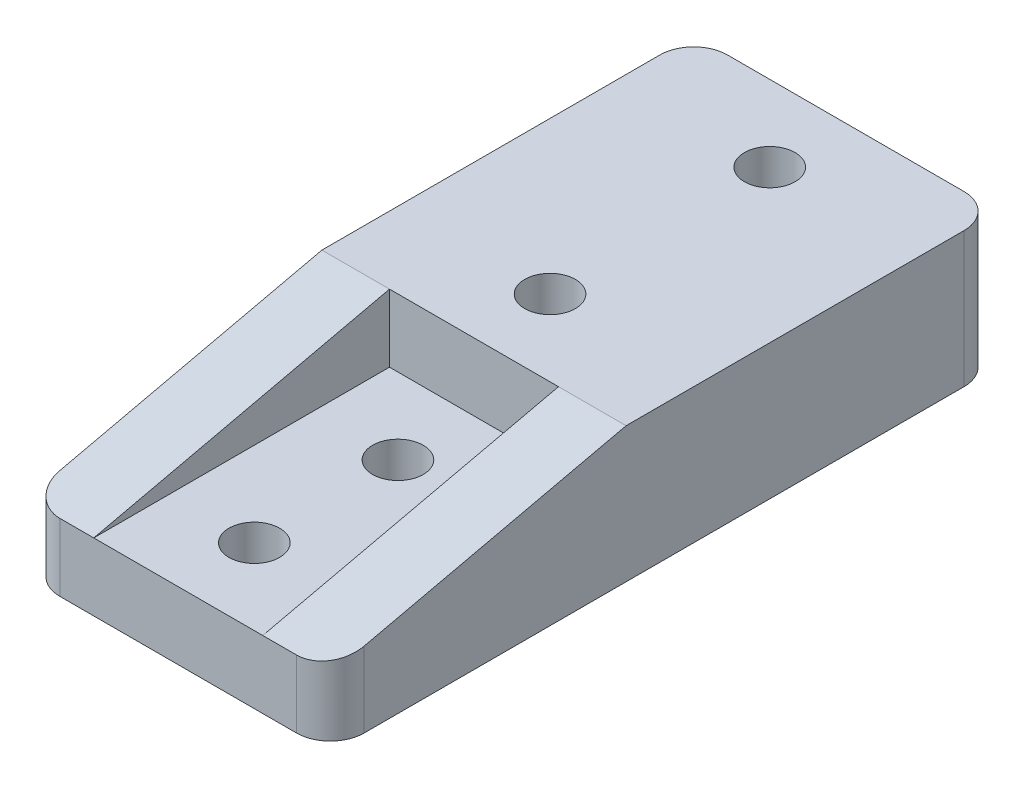
SolidWorks part; units mm, degrees
ref_plane "Front Plane" through (0, 0, 0) normal (0, 0, 1) x (1, 0, 0)
ref_plane "Top Plane" through (0, 0, 0) normal (0, 1, 0) x (1, 0, 0)
ref_plane "Right Plane" through (0, 0, 0) normal (1, 0, 0) x (0, 0, -1)
sketch "Sketch1" plane through (0, 0, 0) normal (0, 1, 0) x (1, 0, 0)
  line L1 (-9, 11.5) -> (9, 11.5)
  line L2 (-9, 11.5) -> (-9, -28)
  line L3 (-9, -28) -> (9, -28)
  line L4 (9, 11.5) -> (9, -28)
extrude "Extrude1" add sketch "Sketch1" along normal blind 8
sketch "Sketch4" plane through (0, 8, 0) normal (0, 1, 0) x (-1, 0, 0)
  line L0 (5, 28) -> (5, 10.5)
  line L3 (9, 28) -> (-9, 28) construction
  line L4 (5, 10.5) -> (-5, 10.5)
  line L5 (-5, 10.5) -> (-5, 28)
  line L6 (-5, 28) -> (5, 28)
  circle A0 centre (0, -7) radius 1.5
  circle A1 centre (0, 6) radius 1.5
  line M2 (9, 28) -> (-9, 28)
extrude "Extrude3" cut sketch "Sketch4" against normal blind 4 contours L5 L4 L0 M2 region at (0, 8, 19.25)
sketch "Sketch7" plane through (9, 0, 0) normal (1, 0, 0) x (0, 0, -1)
  line L0 (-28, 4) -> (-10.5, 8)
  line L1 (-28, 8) -> (-28, 0) construction
  line L2 (-28, 8) -> (11.5, 8) construction
  line L3 (-28, 4) -> (-28, 8)
  line L4 (-28, 8) -> (-10.5, 8)
extrude "Extrude4" cut sketch "Sketch7" against normal through all
extrude "Extrude5" cut sketch "Sketch4<4>" against normal through all contours A1 | A0 region at (0, 8, -7) region at (0, 8, 6)
sketch "Sketch4<4>" plane through (0, 8, 0) normal (0, 1, 0) x (-1, 0, 0) same geometry as "Sketch4"
fillet "Fillet1" radius 2 2 edges at (-9, 2, 28) (9, 2, 28)
sketch "Sketch8" plane through (0, 4, 0) normal (0, 1, 0) x (-1, 0, 0)
  circle A0 centre (0, 15) radius 1.5
  circle A1 centre (0, 23.5) radius 1.5
extrude "Extrude6" cut sketch "Sketch8" against normal through all
sketch "Sketch9" plane through (0, 0, 0) normal (0, -1, 0) x (1, 0, 0)
  circle A0 centre (0, 6) radius 3.5
extrude "Extrude7" cut sketch "Sketch9" against normal blind 3
fillet "Fillet2" radius 2 2 edges at (-9, 4, -11.5) (9, 4, -11.5)
